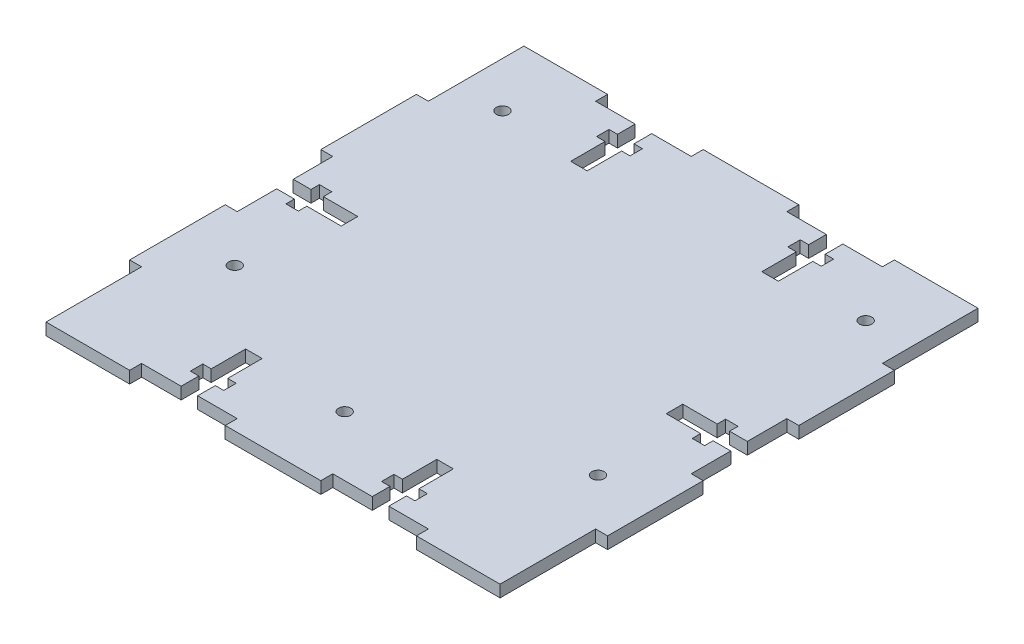
SolidWorks part; units mm, degrees
ref_plane "Front Plane" through (0, 0, 0) normal (0, 0, 1) x (1, 0, 0)
ref_plane "Top Plane" through (0, 0, 0) normal (0, 1, 0) x (1, 0, 0)
ref_plane "Right Plane" through (0, 0, 0) normal (1, 0, 0) x (0, 0, -1)
sketch "Sketch1" plane through (0, 0, 0) normal (0, 1, 0) x (1, 0, 0)
  line L1 (0, 0) -> (127, 0)
  line L2 (0, 0) -> (0, 127)
  line L3 (0, 127) -> (127, 127)
  line L4 (127, 0) -> (127, 127)
  dimension "D1" = 127
  dimension "D2" = 127
extrude "Boss-Extrude1" add sketch "Sketch1" along normal blind 3.175
sketch "Sketch2" plane through (0, 3.175, 0) normal (0, 1, 0) x (1, 0, 0)
  line L1 (0, 127) -> (3.175, 127)
  line L2 (0, 127) -> (0, 101.6)
  line L3 (0, 101.6) -> (3.175, 101.6)
  line L4 (3.175, 127) -> (3.175, 101.6)
  dimension "D1" = 25.4
  dimension "D2" = 3.175
extrude "Cut-Extrude1" cut sketch "Sketch2" against normal blind 6.35
pattern_linear "LPattern1" count 3 spacing 50.8 along (0, 0, 1) count 2 spacing 123.825 along (1, 0, 0) of "Cut-Extrude1"
sketch "Sketch3" plane through (0, 3.175, 0) normal (0, 1, 0) x (1, 0, 0)
  line L0 (3.175, 0) -> (123.825, 0) construction
  line L1 (25.4, 0) -> (50.8, 0)
  line L2 (25.4, 0) -> (25.4, 3.175)
  line L3 (25.4, 3.175) -> (50.8, 3.175)
  line L4 (50.8, 0) -> (50.8, 3.175)
  line L5 (0, 50.8) -> (0, 25.4) construction
  dimension "D1" = 25.4
  dimension "D2" = 3.175
  dimension "D3" = 25.4
extrude "Cut-Extrude2" cut sketch "Sketch3" against normal blind 6.35
pattern_linear "LPattern2" count 3 spacing 50.8 along (1, 0, 0) count 2 spacing 123.825 along (0, 0, -1) of "Cut-Extrude2"
ref_plane "Plane1" through (0, 0, -63.5) normal (0, 0, 1) x (1, 0, 0)
sketch "Sketch4" plane through (0, 3.175, 0) normal (0, 1, 0) x (1, 0, 0)
  line L0 (123.825, 76.2) -> (123.825, 50.8) construction
  line L1 (123.825, 65.6971) -> (106.68, 65.6971)
  line L2 (123.825, 65.6971) -> (123.825, 61.3029)
  line L3 (123.825, 61.3029) -> (106.68, 61.3029)
  line L4 (106.68, 65.6971) -> (106.68, 61.3029)
  line L5 (127, 76.2) -> (123.825, 76.2) construction
  line L7 (115.824, 67.945) -> (119.126, 67.945)
  line L8 (115.824, 67.945) -> (115.824, 59.055)
  line L9 (115.824, 59.055) -> (119.126, 59.055)
  line L10 (119.126, 67.945) -> (119.126, 59.055)
  point P6 (123.825, 63.5)
  point P13 (117.475, 59.055)
  point P14 (119.126, 63.5)
  dimension "D1" = 17.145
  dimension "D2" = 4.3942
  dimension "D3" = 12.7
  dimension "D4" = 3.302
  dimension "D5" = 6.35
  dimension "D6" = 8.89
  dimension "D7" = 12.7
extrude "Cut-Extrude3" cut sketch "Sketch4" against normal blind 8.89 contours L1 L4 L3 L2 | L7 L10 L9 L8
sketch "Sketch5" plane through (0, 3.175, 0) normal (0, 1, 0) x (1, 0, 0)
  line L0 (50.8, 3.175) -> (25.4, 3.175) construction
  line L1 (35.9029, 3.175) -> (40.2971, 3.175)
  line L2 (35.9029, 3.175) -> (35.9029, 20.32)
  line L3 (35.9029, 20.32) -> (40.2971, 20.32)
  line L4 (40.2971, 3.175) -> (40.2971, 20.32)
  line L5 (50.8, 0) -> (50.8, 3.175) construction
  line L6 (33.655, 11.176) -> (42.545, 11.176)
  line L7 (33.655, 11.176) -> (33.655, 7.874)
  line L8 (33.655, 7.874) -> (42.545, 7.874)
  line L9 (42.545, 11.176) -> (42.545, 7.874)
  point P6 (38.1, 20.32)
  point P12 (38.1, 7.874)
  point P15 (42.545, 9.525)
  dimension "D1" = 17.145
  dimension "D2" = 4.3942
  dimension "D3" = 12.7
  dimension "D4" = 3.302
  dimension "D5" = 8.89
  dimension "D6" = 12.7
  dimension "D7" = 6.35
extrude "Cut-Extrude4" cut sketch "Sketch5" against normal blind 30.48 contours L3 L4 L1 L2 | L7 L8 L9 L6
pattern_linear "LPattern3" count 2 spacing 50.8 along (1, 0, 0) of "Cut-Extrude4"
sketch "Sketch10" plane through (0, 3.175, 0) normal (0, 1, 0) x (1, 0, 0)
  line L1 (78.7908, 104.775) -> (101.6, 104.775)
  line L2 (78.7908, 104.775) -> (78.7908, 48.8442)
  line L3 (78.7908, 48.8442) -> (101.6, 48.8442)
  line L4 (101.6, 104.775) -> (101.6, 48.8442)
  line L5 (76.2, 123.825) -> (101.6, 123.825) construction
  line L6 (127, 76.2) -> (127, 101.6) construction
  dimension "D1" = 22.8092
  dimension "D2" = 55.9308
  dimension "D3" = 25.4
  dimension "D4" = 19.05
mirror "Mirror2" about plane through (0, 0, -63.5) normal (0, 0, 1) of "LPattern3"
sketch "2x2_PCB" plane through (0, 3.175, 0) normal (0, 1, 0) x (1, 0, 0)
  line L0 (106.68, 65.6971) -> (106.68, 61.3029) construction
  line L1 (10.16, 90.551) -> (60.96, 90.551)
  line L2 (10.16, 90.551) -> (10.16, 36.449)
  line L3 (10.16, 36.449) -> (60.96, 36.449)
  line L4 (60.96, 90.551) -> (60.96, 36.449)
  line L5 (10.16, 90.551) -> (60.96, 36.449) construction
  line L6 (10.16, 36.449) -> (60.96, 90.551) construction
  line L8 (0, 101.6) -> (0, 76.2) construction
  point P0 (35.56, 63.5)
  point P7 (106.68, 63.5)
  point P8 (35.56, 90.551)
  dimension "D1" = 50.8
  dimension "D2" = 54.102
  dimension "D3" = 35.56
hole_wizard "#4 Clearance Hole4" positions "Sketch18" profile "Sketch16" hole size "#4" standard "ANSI Inch"
sketch "Sketch18" plane through (0, 3.175, 0) normal (0, 1, 0) x (1, 0, 0)
  line L0 (127, 25.4) -> (127, 50.8) construction
  line L2 (50.8, 0) -> (76.2, 0) construction
  point P0 (63.5, 19.05)
  dimension "D1" = 63.5
  dimension "D2" = 19.05
sketch "Sketch16" plane through (63.5, 3.175, -19.05) normal (1, 0, 0) x (0, 0, 1)
  line L0 (0, 0) -> (0, 11.1406)
  line L1 (0, 11.1406) -> (1.6319, 10.16)
  line L2 (1.6319, 10.16) -> (1.6319, 0)
  line L5 (1.6319, 0) -> (0, 0)
  line L10 (0, 11.1406) -> (-1.632, 10.16) construction
  line L11 (0, -6.35) -> (0, 107.95) construction
  dimension "Hole Dia." = 3.2639
  dimension "Hole Depth" = 10.16
  dimension "Drill Angle" = 118
ref_plane "Plane2" through (63.5, 0, 0) normal (-1, 0, 0) x (0, 0, 1)
mirror "Mirror3" about plane through (63.5, 0, 0) normal (-1, 0, 0) of "Cut-Extrude3"
sketch "Sketch19" plane through (0, 3.175, 0) normal (0, 1, 0) x (1, 0, 0)
  line L0 (0, 101.6) -> (0, 76.2) construction
  line L1 (12.7, 111.76) -> (114.3, 111.76)
  line L2 (12.7, 111.76) -> (12.7, 35.56)
  line L3 (12.7, 35.56) -> (114.3, 35.56)
  line L4 (114.3, 111.76) -> (114.3, 35.56)
  line L5 (76.2, 127) -> (50.8, 127) construction
  dimension "D1" = 101.6
  dimension "D2" = 76.2
  dimension "D3" = 12.7
  dimension "D4" = 15.24
hole_wizard "#4 Clearance Hole5" positions "Sketch21" profile "Sketch20" hole size "#4" standard "ANSI Inch"
sketch "Sketch21" plane through (0, 3.175, 0) normal (0, 1, 0) x (1, 0, 0)
  line L0 (12.7, 111.76) -> (12.7, 35.56) construction
  line L1 (12.7, 111.76) -> (114.3, 111.76) construction
  line L2 (114.3, 111.76) -> (114.3, 35.56) construction
  line L3 (12.7, 35.56) -> (114.3, 35.56) construction
  point P0 (15.24, 109.22)
  point P2 (111.76, 109.22)
  point P4 (111.76, 38.1)
  point P6 (15.24, 38.1)
  dimension "D1" = 2.54
  dimension "D2" = 2.54
  dimension "D3" = 2.54
  dimension "D4" = 2.54
sketch "Sketch20" plane through (15.24, 3.175, -109.22) normal (1, 0, 0) x (0, 0, 1)
  line L0 (0, 0) -> (0, 11.1406)
  line L1 (0, 11.1406) -> (1.6319, 10.16)
  line L2 (1.6319, 10.16) -> (1.6319, 0)
  line L5 (1.6319, 0) -> (0, 0)
  line L10 (0, 11.1406) -> (-1.6319, 10.16) construction
  line L11 (0, -6.35) -> (0, 107.95) construction
  dimension "Hole Dia." = 3.2639
  dimension "Hole Depth" = 10.16
  dimension "Drill Angle" = 118
